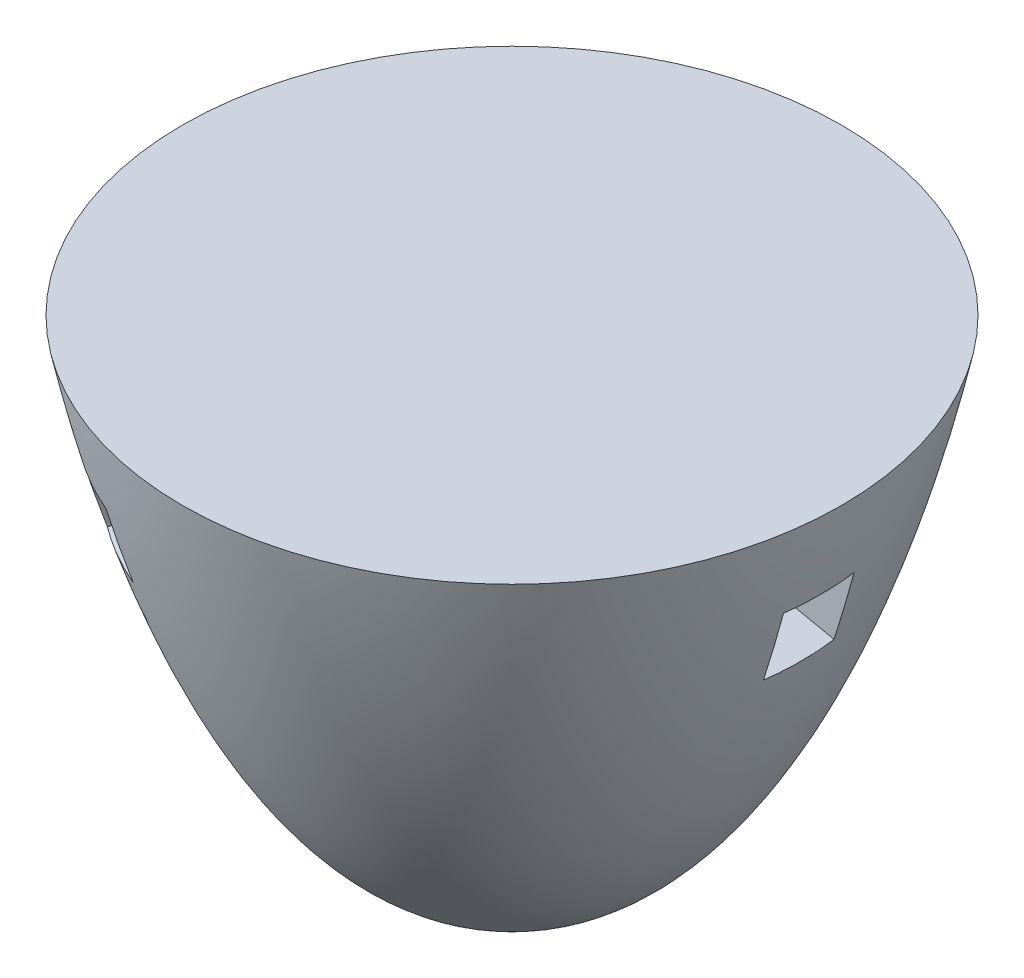
SolidWorks part; units mm, degrees
ref_plane "Plan de face" through (0, 0, 0) normal (0, 0, 1) x (1, 0, 0)
ref_plane "Plan de dessus" through (0, 0, 0) normal (0, 1, 0) x (1, 0, 0)
ref_plane "Plan de droite" through (0, 0, 0) normal (1, 0, 0) x (0, 0, -1)
sketch "Esquisse1" plane through (0, 0, 0) normal (0, 0, 1) x (1, 0, 0)
  line L0 (-14, 4.8625) -> (0, 4.8625)
  line L1 (0, 4.8625) -> (0, -16)
  spline S0 degree 3 poles (-14, 4.8625) (-12.0858, -4.3313) (-7.6152, -16.3383) (0, -16) knots 0 0 0 0 1 1 1 1
  dimension "D2" = 14
  dimension "D3" = 16
revolve "Révolution1" add sketch "Esquisse1" angle 360 about L1
sketch "Esquisse2" plane through (0, 0, 0) normal (0, 0, 1) x (1, 0, 0)
  line L2 (13.2199, 1.1278) -> (8.3256, 2.15)
  line L3 (13.2199, 1.1278) -> (12.6066, -1.8089)
  line L4 (12.6066, -1.8089) -> (7.7122, -0.7866)
  line L5 (8.3256, 2.15) -> (7.7122, -0.7866)
  spline S2 degree 3 poles (0.3139, -16.007) (0.3357, -16.0069) (0.3793, -16.0068) (0.4447, -16.0059) (0.5099, -16.0043) (0.5749, -16.0022) (0.6397, -15.9995) (0.7044, -15.9961) (0.769, -15.9922) (0.8344, -15.9876) (0.9007, -15.9823) (0.9678, -15.9762) (1.0347, -15.9695) (1.1015, -15.9622) (1.1681, -15.9542) (1.2345, -15.9456) (1.3008, -15.9363) (1.3668, -15.9264) (1.4327, -15.9158) (1.4985, -15.9047) (1.564, -15.8929) (1.6282, -15.8807) (1.6909, -15.8682) (1.7522, -15.8553) (1.8134, -15.8419) (1.8745, -15.828) (1.9366, -15.8132) (1.9997, -15.7976) (2.064, -15.781) (2.128, -15.7639) (2.1919, -15.7461) (2.2556, -15.7277) (2.318, -15.7091) (2.3789, -15.6903) (2.4385, -15.6713) (2.498, -15.6519) (2.5573, -15.6318) (2.6187, -15.6105) (2.6823, -15.5878) (2.7479, -15.5636) (2.8134, -15.5388) (2.8787, -15.5134) (2.9438, -15.4873) (3.0086, -15.4606) (3.0734, -15.4332) (3.1368, -15.4057) (3.199, -15.3781) (3.26, -15.3504) (3.3208, -15.3221) (3.3814, -15.2933) (3.4419, -15.2639) (3.5057, -15.2322) (3.573, -15.198) (3.6436, -15.1613) (3.714, -15.1238) (3.7816, -15.087) (3.8465, -15.0508) (3.9087, -15.0155) (3.9708, -14.9795) (4.0327, -14.943) (4.0943, -14.9059) (4.1558, -14.8682) (4.2171, -14.83) (4.2812, -14.7893) (4.3479, -14.7461) (4.4173, -14.7003) (4.4864, -14.6537) (4.5553, -14.6065) (4.6239, -14.5585) (4.6923, -14.5098) (4.7586, -14.4617) (4.8228, -14.4144) (4.8848, -14.3679) (4.9467, -14.3207) (5.0084, -14.273) (5.0698, -14.2247) (5.1321, -14.1751) (5.195, -14.1241) (5.2588, -14.0716) (5.3223, -14.0185) (5.3856, -13.9649) (5.4486, -13.9106) (5.5115, -13.8556) (5.5762, -13.7983) (5.6428, -13.7383) (5.7111, -13.6758) (5.7792, -13.6126) (5.847, -13.5486) (5.9146, -13.484) (5.9819, -13.4186) (6.0489, -13.3526) (6.1157, -13.2858) (6.1822, -13.2183) (6.248, -13.1506) (6.3132, -13.0826) (6.3778, -13.0144) (6.442, -12.9455) (6.5065, -12.8755) (6.571, -12.8045) (6.6357, -12.7324) (6.7001, -12.6597) (6.7642, -12.5863) (6.8277, -12.5127) (6.8905, -12.4389) (6.9528, -12.365) (7.0147, -12.2905) (7.0769, -12.2148) (7.1392, -12.1381) (7.2016, -12.0602) (7.2638, -11.9817) (7.3257, -11.9026) (7.3874, -11.8229) (7.4488, -11.7427) (7.5099, -11.6619) (7.5707, -11.5806) (7.6311, -11.4987) (7.6914, -11.4163) (7.7513, -11.3334) (7.8107, -11.2504) (7.8694, -11.1673) (7.9275, -11.0843) (7.9854, -11.0007) (8.0434, -10.916) (8.1016, -10.8302) (8.1599, -10.7433) (8.2179, -10.6559) (8.2757, -10.568) (8.3332, -10.4796) (8.3904, -10.3906) (8.4506, -10.2962) (8.5136, -10.1962) (8.5794, -10.0906) (8.6449, -9.9843) (8.71, -9.8774) (8.7747, -9.7698) (8.8379, -9.6637) (8.8995, -9.559) (8.9596, -9.4559) (9.0194, -9.3522) (9.0788, -9.248) (9.1395, -9.1405) (9.2014, -9.0298) (9.2645, -8.9158) (9.3271, -8.8012) (9.3894, -8.686) (9.4514, -8.5702) (9.5118, -8.4561) (9.5707, -8.3437) (9.6282, -8.2331) (9.6853, -8.1219) (9.7421, -8.0103) (9.8008, -7.8939) (9.8613, -7.7727) (9.9235, -7.6465) (9.9854, -7.5198) (10.0469, -7.3926) (10.108, -7.2649) (10.1687, -7.1366) (10.229, -7.0079) (10.2889, -6.8786) (10.3484, -6.7489) (10.4075, -6.6187) (10.4662, -6.488) (10.5246, -6.3569) (10.5825, -6.2254) (10.6401, -6.0934) (10.6973, -5.961) (10.755, -5.8261) (10.8132, -5.6886) (10.8718, -5.5487) (10.93, -5.4083) (10.9878, -5.2675) (11.0452, -5.1263) (11.1039, -4.9804) (11.1638, -4.8299) (11.2249, -4.6746) (11.2856, -4.5189) (11.3457, -4.3628) (11.4054, -4.2064) (11.4645, -4.0496) (11.5251, -3.8872) (11.5871, -3.7192) (11.6504, -3.5455) (11.7131, -3.3716) (11.7752, -3.1972) (11.8367, -3.0226) (11.8976, -2.8477) (11.9579, -2.6724) (12.0176, -2.497) (12.0767, -2.3213) (12.1349, -2.1464) (12.1921, -1.9724) (12.2484, -1.7992) (12.3041, -1.6259) (12.3607, -1.4479) (12.4182, -1.2651) (12.4765, -1.0776) (12.534, -0.89) (12.591, -0.7024) (12.6472, -0.5147) (12.7018, -0.3306) (12.7546, -0.1501) (12.8058, 0.0268) (12.8565, 0.2037) (12.9065, 0.3805) (12.956, 0.5571) (13.0049, 0.7337) (13.0532, 0.9101) (13.1009, 1.0864) (13.148, 1.2625) (13.1943, 1.4374) (13.2397, 1.611) (13.2843, 1.7833) (13.3283, 1.9554) (13.372, 2.1282) (13.4155, 2.3018) (13.4586, 2.4761) (13.5011, 2.6501) (13.5431, 2.8237) (13.5842, 2.9959) (13.6245, 3.1667) (13.6641, 3.336) (13.7031, 3.505) (13.7401, 3.6675) (13.7753, 3.8235) (13.8087, 3.9732) (13.8417, 4.1224) (13.8742, 4.2713) (13.9063, 4.4197) (13.938, 4.5677) (13.9692, 4.7153) (13.9898, 4.8135) (14, 4.8625) knots 0 0 0 0 0.002461 0.004917 0.007367 0.009812 0.012252 0.014687 0.017117 0.019543 0.02208 0.024612 0.027141 0.029665 0.032186 0.034703 0.037217 0.039728 0.042236 0.044741 0.047245 0.049746 0.052102 0.054458 0.056811 0.059164 0.061516 0.064009 0.066502 0.068995 0.071487 0.073979 0.076471 0.078821 0.081172 0.083523 0.085875 0.088228 0.090856 0.093485 0.096116 0.098748 0.101383 0.104021 0.106661 0.109303 0.111817 0.114334 0.116854 0.119377 0.121903 0.124433 0.127419 0.13041 0.133406 0.136408 0.139093 0.141783 0.144478 0.147177 0.149882 0.152592 0.155308 0.158029 0.161146 0.16427 0.167402 0.170542 0.17369 0.176846 0.180011 0.182919 0.185834 0.188757 0.191687 0.194625 0.19757 0.200663 0.203765 0.206875 0.209994 0.213122 0.216258 0.219404 0.222874 0.226355 0.229848 0.233351 0.236866 0.240392 0.243929 0.247477 0.251037 0.254608 0.258127 0.261657 0.265198 0.26875 0.272378 0.276018 0.279669 0.283332 0.287007 0.290627 0.294259 0.297902 0.301556 0.305296 0.309048 0.312811 0.316586 0.320373 0.324171 0.32798 0.331793 0.335617 0.339452 0.343299 0.347157 0.350957 0.354767 0.358589 0.362421 0.366342 0.370274 0.374216 0.37817 0.382134 0.386109 0.390095 0.394758 0.399435 0.404126 0.408832 0.41355 0.418283 0.422757 0.427243 0.431741 0.436251 0.440771 0.445655 0.450552 0.455462 0.460384 0.465319 0.470265 0.474941 0.479626 0.484322 0.489028 0.493744 0.499019 0.504307 0.509605 0.514916 0.520238 0.52557 0.530914 0.536268 0.541632 0.547006 0.55239 0.557783 0.563186 0.568597 0.574017 0.579445 0.585141 0.590845 0.596557 0.602278 0.608005 0.61374 0.620004 0.626276 0.632555 0.638842 0.645134 0.651433 0.657737 0.664677 0.671623 0.678573 0.685529 0.692487 0.699449 0.706413 0.713379 0.720347 0.727315 0.734158 0.741001 0.747842 0.754682 0.762065 0.769444 0.776819 0.784189 0.791552 0.798909 0.805838 0.812761 0.819674 0.82658 0.833475 0.840361 0.847236 0.854099 0.860951 0.867789 0.874493 0.881182 0.887858 0.894518 0.901284 0.908033 0.914764 0.921477 0.928171 0.934727 0.941263 0.947778 0.954273 0.960054 0.965817 0.971562 0.977289 0.982996 0.988684 0.994352 1 1 1 1 construction
  dimension "D1" = 3
  dimension "D2" = 5
extrude "Enlèv. mat.-Extru.1" cut sketch "Esquisse2" against normal blind 1.5 and the other way blind 1.5
pattern_circular "Répétition circulaire1" count 3 over 360 about axis through (0, 4.8625, 0) along (0, 1, 0) of "Enlèv. mat.-Extru.1"
